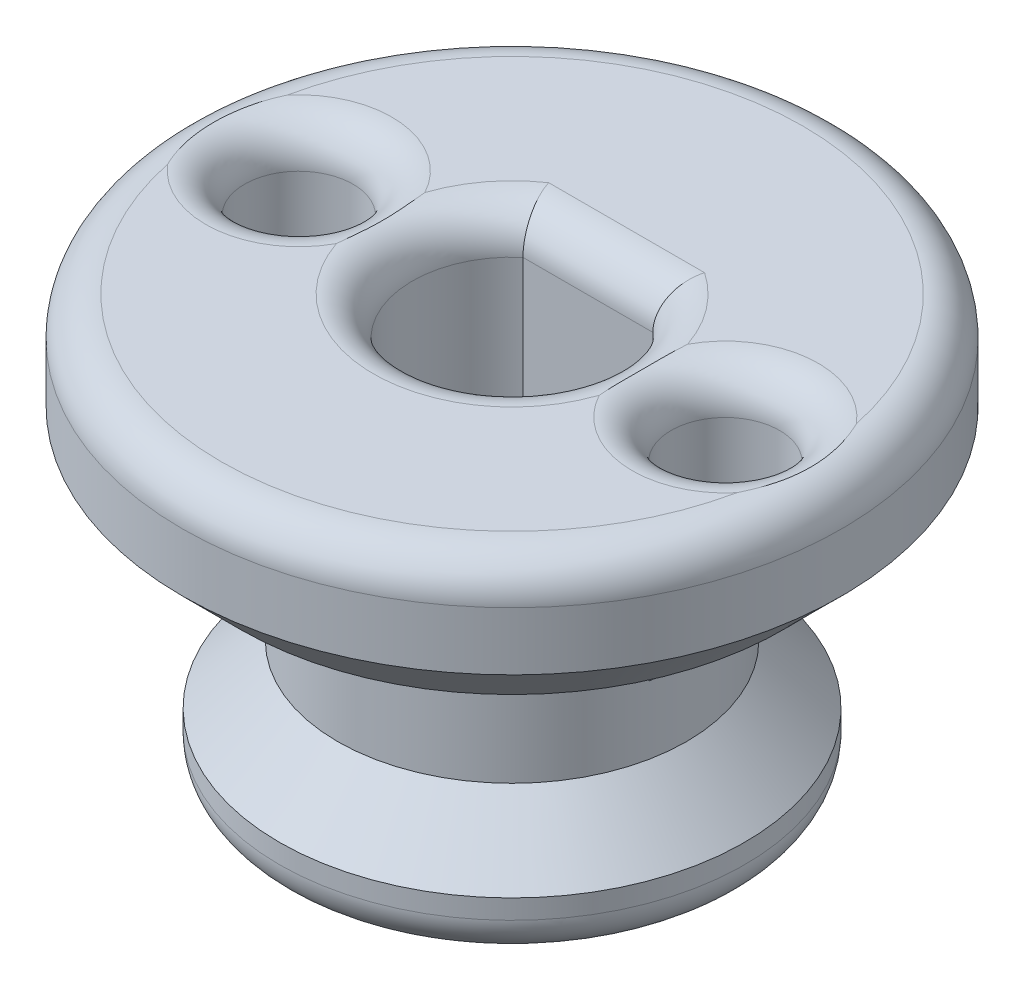
SolidWorks part; units mm, degrees
ref_plane "Front Plane" through (0, 0, 0) normal (0, 0, 1) x (1, 0, 0)
ref_plane "Top Plane" through (0, 0, 0) normal (0, 1, 0) x (1, 0, 0)
ref_plane "Right Plane" through (0, 0, 0) normal (1, 0, 0) x (0, 0, -1)
ref_axis "X Axis" through (-88.99, 0, 0) along (1, 0, 0)
ref_axis "Y Axiz" through (0, 0, 55) along (0, 0, -1)
ref_axis "Z Axis" through (0, 55, 0) along (0, -1, 0)
sketch "Sketch1" plane through (0, 0, 0) normal (0, 1, 0) x (1, 0, 0)
  line L0 (1.675, 1.9558) -> (-1.675, 1.9558)
  arc A0 (-1.675, 1.9558) -> (1.675, 1.9558) centre (0, 0) ccw
  circle A1 centre (0, 0) radius 4.5
  circle A2 centre (0, 0) radius 6
  dimension "D1" = 5.15
  dimension "D3" = 9
  dimension "D4" = 12
  dimension "D2" = 3.35
extrude "Boss-Extrude1" add sketch "Sketch1" along normal blind 10.75 contours A1 A0 L0 region at (-4.3727, 0, 0)
extrude "Boss-Extrude2" add sketch "Sketch1<5>" along normal blind 3 contours A1 A0 L0 | L0 A0 | A2 region at (0, 0, 0.1614) region at (-4.3727, 0, 0)
sketch "Sketch1<5>" plane through (0, 0, 0) normal (0, 1, 0) x (1, 0, 0) same geometry as "Sketch1"
ref_plane "Plane1" through (0, 5.375, 0) normal (0, 1, 0) x (1, 0, 0)
sketch "Sketch2" plane through (0, 10.75, 0) normal (0, 1, 0) x (1, 0, 0)
  line L0 (-1.675, 1.9558) -> (1.675, 1.9558)
  arc A0 (-1.675, 1.9558) -> (1.675, 1.9558) centre (0, 0) ccw
  circle A1 centre (0, 0) radius 8.5
  dimension "D1" = 17
extrude "Boss-Extrude3" add sketch "Sketch2" against normal blind 4
chamfer "Chamfer1" distance 1.5 angle 45 5 edges at (0, 3, 6) (0, 0, -1.9558) (0, 0, 2.575) (0, 6.75, 4.5) (0, 6.75, 8.5)
sketch "Sketch3" plane through (0, 10.75, 0) normal (0, 1, 0) x (1, 0, 0)
  line L1 (-6.0287, 0) -> (6.0287, 0) construction
  circle A0 centre (5.5, 0) radius 1.4
  circle A1 centre (5.5, 0) radius 2.75 construction
  circle A2 centre (-5.5, 0) radius 1.4
  point P10 (0, 0)
  dimension "D1" = 2.8
  dimension "D3" = 5.5
  dimension "D2" = 5.5
  dimension "D4" = 2
extrude "Cut-Extrude1" cut sketch "Sketch3" against normal blind 6
fillet "Fillet1" radius 1 8 edges at (0, 10.75, -1.9558) (0, 10.75, 2.575) (0, 0, 6) (0, 0, -3.4558) (0, 0, 4.075) (0, 10.75, 8.5) (-5.5, 10.75, 1.4) (5.5, 10.75, 1.4)
